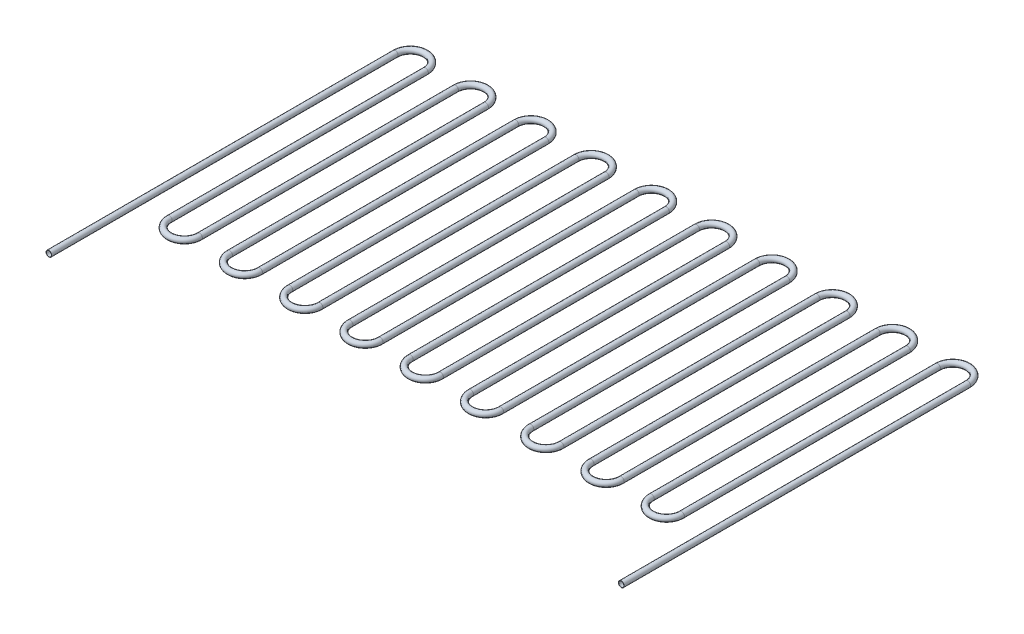
SolidWorks part; units mm, degrees
ref_plane "Front Plane" through (0, 0, 0) normal (0, 0, 1) x (1, 0, 0)
ref_plane "Top Plane" through (0, 0, 0) normal (0, 1, 0) x (1, 0, 0)
ref_plane "Right Plane" through (0, 0, 0) normal (1, 0, 0) x (0, 0, -1)
sketch "Sketch4" plane through (0, 0, 0) normal (0, 1, 0) x (1, 0, 0)
  line L0 (928.1885, -446.1355) -> (928.1885, 403.8645)
  line L1 (978.1885, -521.1355) -> (-1021.8115, -521.1355) construction
  line L2 (978.1885, -521.1355) -> (978.1885, 478.8645) construction
  line L3 (978.1885, 478.8645) -> (-1021.8115, 478.8645) construction
  line L4 (-1021.8115, -521.1355) -> (-1021.8115, 478.8645) construction
  line L5 (828.1885, -446.1355) -> (828.1885, 403.8645)
  line L6 (728.1885, -446.1355) -> (728.1885, 403.8645)
  line L7 (628.1885, -446.1355) -> (628.1885, 403.8645)
  line L8 (528.1885, -446.1355) -> (528.1885, 403.8645)
  line L9 (428.1885, -446.1355) -> (428.1885, 403.8645)
  line L10 (328.1885, -446.1355) -> (328.1885, 403.8645)
  line L11 (228.1885, -446.1355) -> (228.1885, 403.8645)
  line L12 (128.1885, -446.1355) -> (128.1885, 403.8645)
  line L13 (28.1885, -446.1355) -> (28.1885, 403.8645)
  line L14 (-71.8115, -446.1355) -> (-71.8115, 403.8645)
  line L15 (-171.8115, -446.1355) -> (-171.8115, 403.8645)
  line L16 (-271.8115, -446.1355) -> (-271.8115, 403.8645)
  line L17 (-371.8115, -446.1355) -> (-371.8115, 403.8645)
  line L18 (-471.8115, -446.1355) -> (-471.8115, 403.8645)
  line L19 (-571.8115, -446.1355) -> (-571.8115, 403.8645)
  line L20 (-671.8115, -446.1355) -> (-671.8115, 403.8645)
  line L21 (-771.8115, -446.1355) -> (-771.8115, 403.8645)
  line L22 (-871.8115, -446.1355) -> (-871.8115, 403.8645)
  line L23 (-971.8115, -446.1355) -> (-971.8115, 403.8645)
  line L24 (-971.8115, -446.1355) -> (-971.8115, -746.1355)
  line L25 (928.1885, -446.1355) -> (928.1885, -746.1355)
  arc A0 (928.1885, 403.8645) -> (828.1885, 403.8645) centre (878.1885, 403.8645) ccw
  arc A1 (728.1885, 403.8645) -> (628.1885, 403.8645) centre (678.1885, 403.8645) ccw
  arc A2 (528.1885, 403.8645) -> (428.1885, 403.8645) centre (478.1885, 403.8645) ccw
  arc A3 (328.1885, 403.8645) -> (228.1885, 403.8645) centre (278.1885, 403.8645) ccw
  arc A4 (28.1885, 403.8645) -> (128.1885, 403.8645) centre (78.1885, 403.8645) cw
  arc A5 (-171.8115, 403.8645) -> (-71.8115, 403.8645) centre (-121.8115, 403.8645) cw
  arc A6 (-371.8115, 403.8645) -> (-271.8115, 403.8645) centre (-321.8115, 403.8645) cw
  arc A7 (-571.8115, 403.8645) -> (-471.8115, 403.8645) centre (-521.8115, 403.8645) cw
  arc A8 (-671.8115, 403.8645) -> (-771.8115, 403.8645) centre (-721.8115, 403.8645) ccw
  arc A9 (-771.8115, -446.1355) -> (-871.8115, -446.1355) centre (-821.8115, -446.1355) cw
  arc A10 (-571.8115, -446.1355) -> (-671.8115, -446.1355) centre (-621.8115, -446.1355) cw
  arc A11 (-371.8115, -446.1355) -> (-471.8115, -446.1355) centre (-421.8115, -446.1355) cw
  arc A12 (-171.8115, -446.1355) -> (-271.8115, -446.1355) centre (-221.8115, -446.1355) cw
  arc A13 (-71.8115, -446.1355) -> (28.1885, -446.1355) centre (-21.8115, -446.1355) ccw
  arc A14 (128.1885, -446.1355) -> (228.1885, -446.1355) centre (178.1885, -446.1355) ccw
  arc A15 (328.1885, -446.1355) -> (428.1885, -446.1355) centre (378.1885, -446.1355) ccw
  arc A16 (628.1885, -446.1355) -> (528.1885, -446.1355) centre (578.1885, -446.1355) cw
  arc A17 (728.1885, -446.1355) -> (828.1885, -446.1355) centre (778.1885, -446.1355) ccw
  arc A18 (-871.8115, 403.8645) -> (-971.8115, 403.8645) centre (-921.8115, 403.8645) ccw
  dimension "D6" = 100
  dimension "D7" = 75
  dimension "D5" = 50
  dimension "D1" = 2000
  dimension "D2" = 1000
  dimension "D3" = 20
  dimension "D4" = 75
  dimension "D8" = 300
sweep "Sweep-Thin1" add path "Sketch4" circular profile diameter 19.05 parameters "D1"=1, "D3"=19.05
